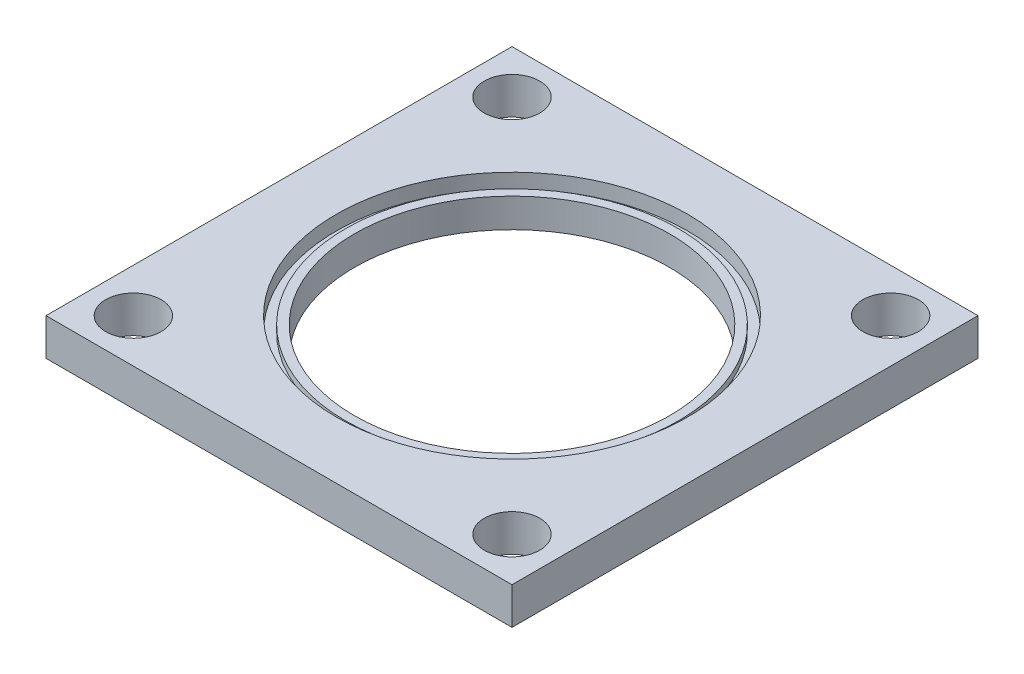
SolidWorks part; units mm, degrees
ref_plane "Front Plane" through (0, 0, 0) normal (0, 0, 1) x (1, 0, 0)
ref_plane "Top Plane" through (0, 0, 0) normal (0, 1, 0) x (1, 0, 0)
ref_plane "Right Plane" through (0, 0, 0) normal (1, 0, 0) x (0, 0, -1)
sketch "plateOutline" plane through (0, 0, 0) normal (0, 1, 0) x (1, 0, 0)
  line L1 (-40, -40) -> (40, -40)
  line L2 (-40, -40) -> (-40, 40)
  line L3 (-40, 40) -> (40, 40)
  line L4 (40, -40) -> (40, 40)
  line L5 (-40, -40) -> (40, 40) construction
  line L6 (-40, 40) -> (40, -40) construction
  line L7 (-40, -40) -> (40, -40) construction
  line L8 (-40, -40) -> (-40, 40) construction
  line L9 (-40, 40) -> (40, 40) construction
  line L10 (40, -40) -> (40, 40) construction
  point P0 (0, 0)
  dimension "D1" = 80
sketch "railGuides" plane through (0, 0, 0) normal (0, 1, 0) x (1, 0, 0)
  line L1 (-32.5, -32.5) -> (32.5, -32.5) construction
  line L2 (-32.5, -32.5) -> (-32.5, 32.5) construction
  line L3 (-32.5, 32.5) -> (32.5, 32.5) construction
  line L4 (32.5, -32.5) -> (32.5, 32.5) construction
  line L6 (-40, 40) -> (-25, 25) construction
  line L7 (40, 40) -> (25, 25) construction
  line L8 (25, -25) -> (40, -40) construction
  line L9 (-40, -40) -> (-25, -25) construction
  line L10 (-40, 40) -> (-25, 25) construction
  circle A0 centre (-32.5, 32.5) radius 4.7625
  circle A1 centre (32.5, 32.5) radius 4.7625
  circle A2 centre (32.5, -32.5) radius 4.7625
  circle A3 centre (-32.5, -32.5) radius 4.7625
sketch "FuelGrainMounting" plane through (0, 0, 0) normal (0, 1, 0) x (1, 0, 0)
  circle A0 centre (0, 0) radius 30.1625
sketch "GasIntake" plane through (0, 0, 0) normal (0, 1, 0) x (1, 0, 0)
  line L0 (-40, 40) -> (40, -40) construction
  circle A0 centre (0, 0) radius 27.051
extrude "Boss-Extrude1" add sketch "plateOutline" along normal blind 6.35 contours L3 L4 L1 L2
extrude "Cut-Extrude1" cut sketch "railGuides" along normal blind 10
extrude "Cut-Extrude2" cut sketch "FuelGrainMounting" along normal blind 5 from offset 5
extrude "Cut-Extrude3" cut sketch "GasIntake" along normal blind 5
sketch "Sketch1" plane through (0, 0, 0) normal (0, 1, 0) x (1, 0, 0)
  circle A0 centre (0, 0) radius 28.575
  circle A2 centre (0, 0) radius 30.1625
  dimension "D1" = 60.325
  dimension "D2" = 57.15
extrude "Cut-Extrude4" cut sketch "Sketch1" against normal blind 1.143 from offset 5
